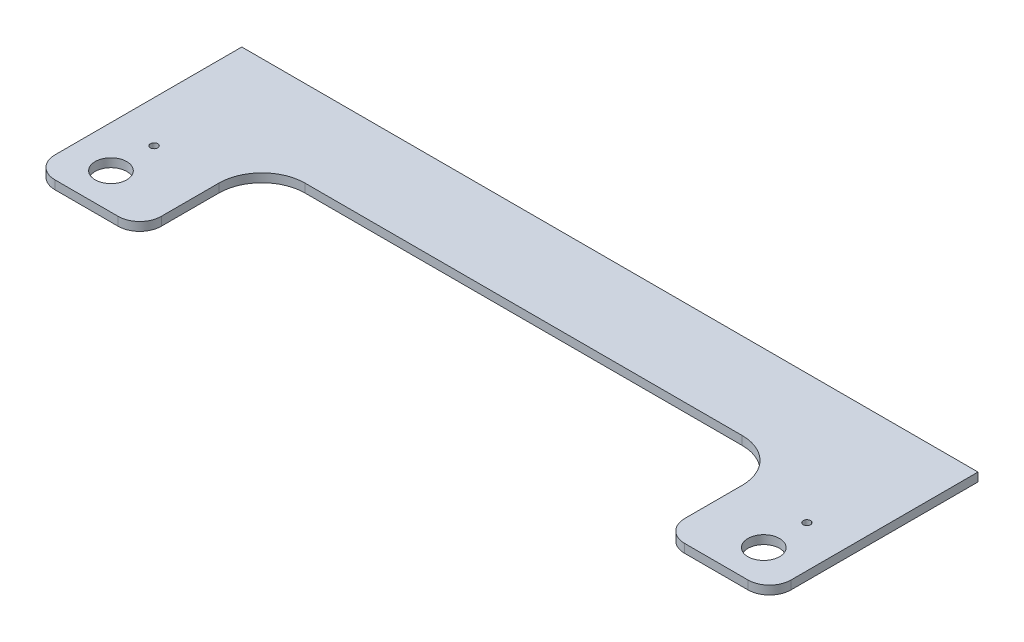
SolidWorks part; units mm, degrees
material "Клен"
ref_plane "Спереди" through (0, 0, 0) normal (0, 0, 1) x (1, 0, 0)
ref_plane "Сверху" through (0, 0, 0) normal (0, 1, 0) x (1, 0, 0)
ref_plane "Справа" through (0, 0, 0) normal (1, 0, 0) x (0, 0, -1)
sketch "Эскиз1" plane through (0, 0, 0) normal (0, 1, 0) x (1, 0, 0)
  line L0 (-322.2029, -10) -> (-322.2029, 120)
  line L5 (-322.2029, 120) -> (189.7971, 120)
  line L6 (189.7971, 120) -> (189.7971, -10)
  line L7 (174.7971, -25) -> (130.7971, -25)
  line L8 (115.7971, -10) -> (115.7971, 30)
  line L9 (85.7971, 60) -> (-218.2029, 60)
  line L10 (-248.2029, 30) -> (-248.2029, -10)
  line L11 (-263.2029, -25) -> (-307.2029, -25)
  line L12 (-276.2029, -25) -> (-316.2029, -25) construction
  line L14 (-316.2029, 120) -> (-322.2029, 120) construction
  line L15 (-322.2029, 360) -> (-322.2029, 120) construction
  line L16 (189.7971, 360) -> (189.7971, 120) construction
  line L18 (-66.2029, 248.8576) -> (-66.2029, -157.5742) construction
  arc A0 (-218.2029, 60) -> (-248.2029, 30) centre (-218.2029, 30) ccw
  arc A1 (115.7971, 30) -> (85.7971, 60) centre (85.7971, 30) ccw
  arc A2 (-248.2029, -10) -> (-263.2029, -25) centre (-263.2029, -10) cw
  arc A3 (130.7971, -25) -> (115.7971, -10) centre (130.7971, -10) cw
  arc A4 (-322.2029, -10) -> (-307.2029, -25) centre (-307.2029, -10) ccw
  arc A5 (189.7971, -10) -> (174.7971, -25) centre (174.7971, -10) cw
  circle A6 centre (-293.2029, 30) radius 2.55
  circle A8 centre (160.7971, 30) radius 2.55
  dimension "D4" = 30
  dimension "D5" = 30
  dimension "D6" = 15
  dimension "D7" = 15
  dimension "D8" = 15
  dimension "D9" = 15
  dimension "D2" = 5.1
  dimension "D3" = 74
  dimension "D10" = 60
  dimension "D12" = 74
extrude "Бобышка-Вытянуть1" add sketch "Эскиз1" along normal blind 6
sketch "Эскиз7" plane through (0, 0, 0) normal (0, 1, 0) x (1, 0, 0)
  circle A1 centre (-293.2029, 0) radius 11
  dimension "D1" = 22
extrude "Вырез-Вытянуть1" cut sketch "Эскиз7" against normal blind 5 and the other way blind 14
sketch "Эскиз8" plane through (0, 0, 0) normal (0, 1, 0) x (1, 0, 0)
  circle A0 centre (160.7971, 0) radius 11
  dimension "D1" = 22
extrude "Вырез-Вытянуть2" cut sketch "Эскиз8" against normal blind 5 and the other way blind 11
